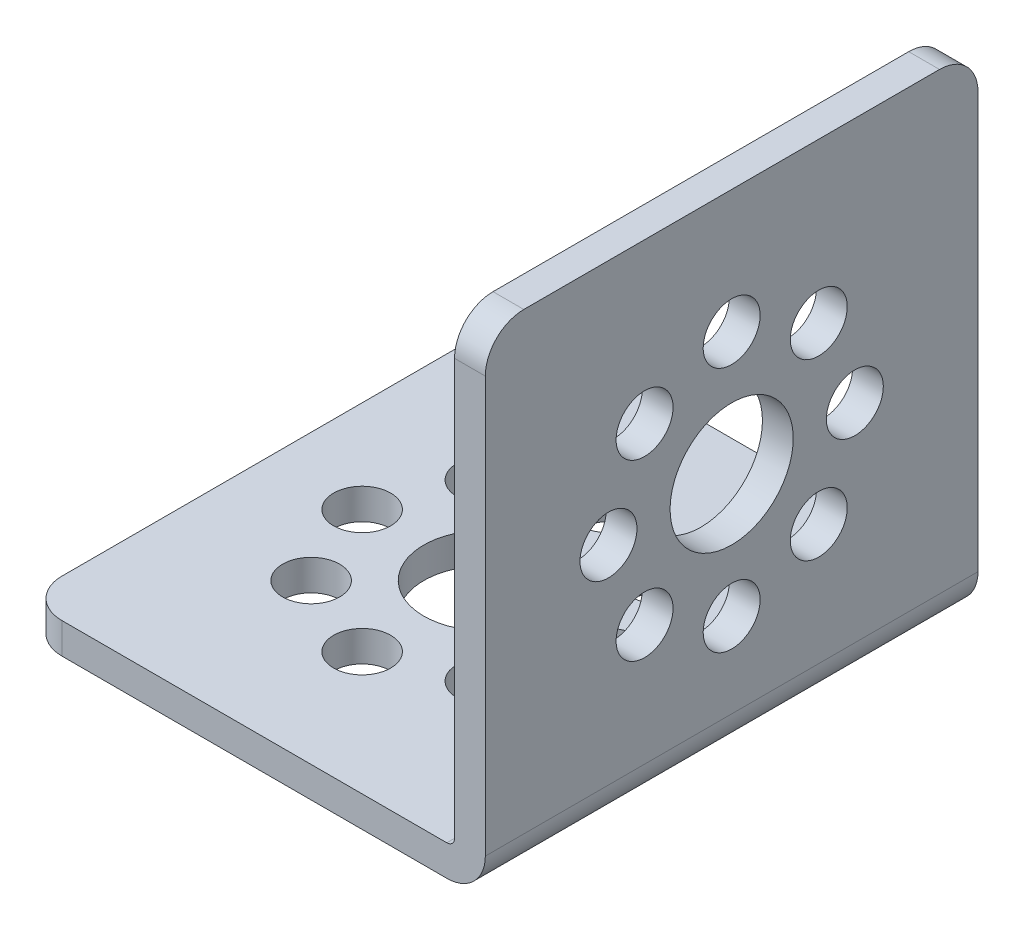
SolidWorks part; units mm, degrees
note: The reader was unsure of these and kept them because the rebuilt part matched: shared geometry of "Sketch3<3>", "Sketch2<4>".
material "5052 Alloy"
ref_plane "Front Plane" through (0, 0, 0) normal (0, 0, 1) x (1, 0, 0)
ref_plane "Top Plane" through (0, 0, 0) normal (0, 1, 0) x (1, 0, 0)
ref_plane "Right Plane" through (0, 0, 0) normal (1, 0, 0) x (0, 0, -1)
sketch "Sketch1" plane through (0, 0, 0) normal (0, 0, 1) x (1, 0, 0)
  line L0 (-13.5, 0) -> (13.5, 0)
  line L1 (16, 2.5) -> (16, 32)
  line L2 (16, 32) -> (14, 32)
  line L3 (14, 32) -> (14, 2.5)
  line L4 (13.5, 2) -> (-13.5, 2)
  line L5 (-14, 2.5) -> (-14, 32)
  line L6 (-14, 32) -> (-16, 32)
  line L7 (-16, 32) -> (-16, 2.5)
  arc A0 (-16, 2.5) -> (-13.5, 0) centre (-13.5, 2.5) ccw
  arc A1 (16, 2.5) -> (13.5, 0) centre (13.5, 2.5) cw
  arc A2 (14, 2.5) -> (13.5, 2) centre (13.5, 2.5) cw
  arc A3 (-13.5, 2) -> (-14, 2.5) centre (-13.5, 2.5) cw
  point P14 (16, 0)
  point P17 (14, 2)
  dimension "D7" = 2.5
  dimension "D8" = 0.5
  dimension "D1" = 32
  dimension "D2" = 2
  dimension "D3" = 2
  dimension "D4" = 2
  dimension "D5" = 32
  dimension "D6" = 32
extrude "Extrude1" add sketch "Sketch1" along normal mid plane 32
fillet "Fillet1" radius 2.5
sketch "Sketch2" plane through (0, 0, 0) normal (0, -1, 0) x (1, 0, 0)
  line B0 (0, 0) -> (8, 0) construction
  circle B1 centre (0, 0) radius 4
  circle B2 centre (8, 0) radius 1.85
  circle B3 centre (0, 0) radius 8 construction
sketch_block_instance "Block-Tetrix Hole Pattern - 8x8x3.7-1"
sketch_block "Block-Tetrix Hole Pattern - 8x8x3.7" parameters "D1"=3.7, "D2"=8, "D3"=16
extrude "Cut-Extrude1" cut sketch "Sketch2" against normal through all contours B1
sketch "Sketch3" plane through (-16, 0, 0) normal (-1, 0, 0) x (0, 0, 1)
  line L0 (13.5, 32) -> (-13.5, 32) construction
  line B0 (0, 16) -> (0, 8) construction
  circle B1 centre (0, 16) radius 4
  circle B2 centre (0, 8) radius 1.85
  circle B3 centre (0, 16) radius 8 construction
  dimension "D1" = 16
sketch_block_instance "Block-Tetrix Hole Pattern - 8x8x3.7-4"
extrude "Cut-Extrude3" cut sketch "Sketch3" against normal through all contours B1
extrude "Cut-Extrude4" cut sketch "Sketch3<3>" against normal through all contours B2
sketch "Sketch3<3>" plane through (-16, 0, 0) normal (-1, 0, 0) x (0, 0, 1) same geometry as "Sketch3"
extrude "Cut-Extrude2" cut sketch "Sketch2<4>" against normal through all contours B2
sketch "Sketch2<4>" plane through (0, 0, 0) normal (0, -1, 0) x (1, 0, 0) same geometry as "Sketch2"
pattern_circular "CirPattern1" count 8 over 360 about axis through (0, 0, 0) along (0, 1, 0) of "Cut-Extrude2"
pattern_circular "CirPattern3" count 8 over 360 about axis through (0, 16, 0) along (1, 0, 0) of "Cut-Extrude4"
sketch "Sketch4" plane through (0, 0, -16) normal (0, 0, -1) x (-1, 0, 0)
  line L0 (14, 2.5) -> (14, -1.1444)
  line L1 (14, -1.1444) -> (16.9158, -1.1444)
  line L2 (16.9158, -1.1444) -> (16.9158, 33.1859)
  line L3 (14, 2.5) -> (14, 33.1859)
  line L4 (14, 33.1859) -> (17.2483, 33.1859)
  arc M6 (13.5, 0) -> (16, 2.5) centre (13.5, 2.5) ccw
  line M7 (16, 2.5) -> (16, 29.5)
  line M8 (16, 29.5) -> (14, 29.5)
  line M9 (14, 29.5) -> (14, 2.5)
extrude "Cut-Extrude5" cut sketch "Sketch4" against normal through all contours L0 M9 M6 M7 M8 | L4 L3 L0 L1 L2 M8 M7 M6
sketch "Sketch5" plane through (0, 0, -16) normal (0, 0, -1) x (-1, 0, 0)
  line L0 (13.5, 2) -> (15.2923, 2)
  line L1 (15.2923, 2) -> (14.3962, 3.9241)
  line L2 (14.3962, 3.9241) -> (13.5, 2)
extrude "Cut-Extrude7" cut sketch "Sketch5" against normal through all
fillet "Fillet2" radius 2.5 2 edges at (-14, 1.0253, 16) (-14, 1.0253, -16)
